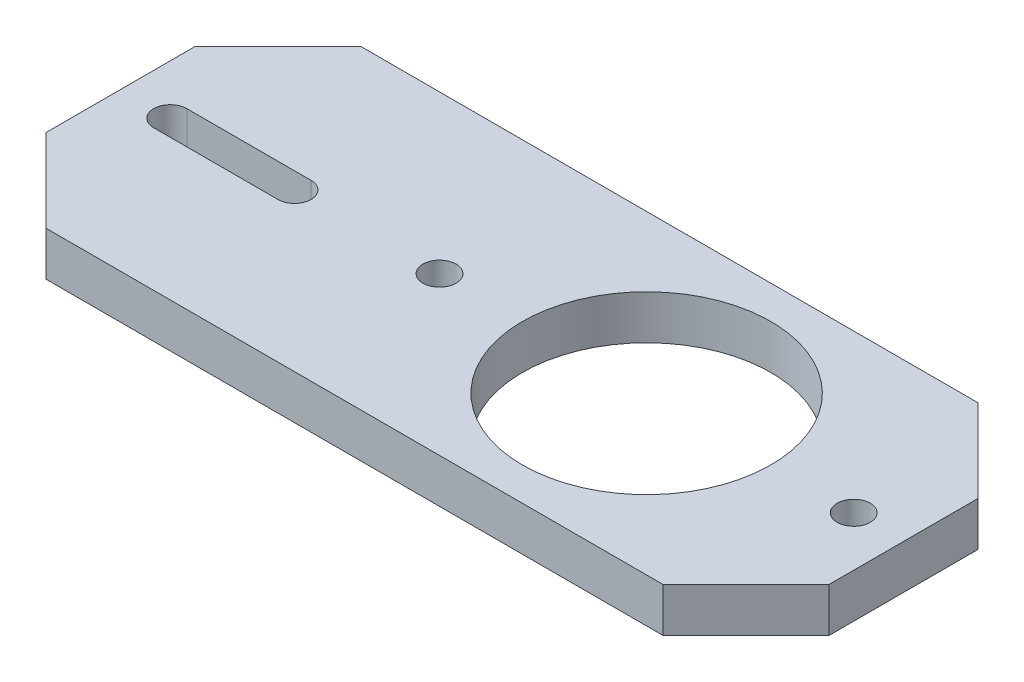
SolidWorks part; units mm, degrees
material "Pine"
ref_plane "Front Plane" through (0, 0, 0) normal (0, 0, 1) x (1, 0, 0)
ref_plane "Top Plane" through (0, 0, 0) normal (0, 1, 0) x (1, 0, 0)
ref_plane "Right Plane" through (0, 0, 0) normal (1, 0, 0) x (0, 0, -1)
sketch "Sketch1" plane through (0, 0, 0) normal (0, 1, 0) x (1, 0, 0)
  line L0 (-57.5, 2) -> (-42.5, 2)
  line L1 (-57.5, -2) -> (-42.5, -2)
  line L2 (-84.5376, 0) -> (67.9764, 0) construction
  line L3 (-50, 2) -> (-50, -2) construction
  line L4 (-63.5, 9) -> (-53.5, 19)
  line L5 (-53.5, 19) -> (21, 19)
  line L6 (-63.5, 9) -> (-63.5, -9)
  line L7 (-53.5, -19) -> (21, -19)
  line L8 (31, 9) -> (31, -9)
  line L9 (-63.5, -9) -> (-53.5, -19)
  line L10 (21, -19) -> (31, -9)
  line L11 (21, 19) -> (31, 9)
  circle A0 centre (-25, 0) radius 2
  circle A1 centre (25, 0) radius 2
  arc A2 (-42.5, -2) -> (-42.5, 2) centre (-42.5, 0) ccw
  arc A4 (-57.5, 2) -> (-57.5, -2) centre (-57.5, 0) ccw
  circle A5 centre (0, 0) radius 15
  point P19 (-63.5, 19)
  point P20 (31, -19)
  point P21 (-63.5, -19)
  point P22 (31, 19)
  dimension "D1" = 4
  dimension "D2" = 4
  dimension "D4" = 4
  dimension "D5" = 75
  dimension "D8" = 4
  dimension "D10" = 30
  dimension "D12" = 6
  dimension "D3" = 50
  dimension "D6" = 15
  dimension "D7" = 6
  dimension "D11" = 25
  dimension "D14" = 19
  dimension "D15" = 19
extrude "Boss-Extrude1" add sketch "Sketch1" against normal blind 5.333
equation "\"rod_diameter\"= 8"
equation "\"rod_hole_thickness\"= 4"
equation "\"rod_radius\"= \"rod_diameter\" / 2"
equation "\"platter_diameter\"= 320"
equation "\"platter_radius\"= \"platter_diameter\" / 2"
equation "\"extruder_mount_hole_spacing\"= 75"
equation "\"arm_rod_spacing\"= 40"
equation "\"motor_level_rod_spacing\"= 15"
equation "\"linear_bearing_diameter\"= 15"
equation "\"z_rod_spacing\"= 75"
equation "\"platter_rod_spacing\"= 50"
equation "\"rod_nut_thickness\"= 6.5"
equation "\"rod_nut_inscribed_diameter\"= 13"
equation "\"z_height\"= 400"
equation "\"gear_pitch\"=2"
equation "\"r_gear_teeth\"= 450"
equation "\"theta_gear_teeth\"= 385"
equation "\"D12@Sketch1\"=2 + \"rod_hole_thickness\""
equation "\"D14@Sketch1\"=15 +\"rod_hole_thickness\""
equation "\"D15@Sketch1\" = 15 + \"rod_hole_thickness\""
equation "\"D7@Sketch1\"=\"rod_hole_thickness\"+2"
equation "\"D5@Sketch1\"=\"extruder_mount_hole_spacing\""
equation "\"top_frame_spacing\"= 100"
equation "\"z_drive_rod_offset\"= 12"
equation "\"sheet_thickness\"=5.333"
equation "\"sheet_tab_hole_thickness\"= \"sheet_thickness\""
equation "\"sheet_tab_width\"= \"sheet_thickness\"*2"
equation "\"sheet_double_tab_width\"= 35"
equation "\"sheet_bolt_diameter\"= 3"
equation "\"sheet_bolt_length\"= 16"
equation "\"sheet_nut_diameter\"= 5.5"
equation "\"sheet_nut_thickness\"= 2.5"
equation "\"sheet_nut_depth\"= 10"
equation "\"bearing_outside_diameter\"= 22"
equation "\"bearing_thickness\"= 7"
equation "\"corner_part_thickness\"= \"sheet_thickness\" + \"bearing_thickness\""
equation "\"setscrew_nut_diameter\"= 6"
equation "\"setscrew_nut_thickness\"= 3"
equation "\"setscrew_bolt_diameter\"= 3"
equation "\"motor_shaft_diameter\"= 5.7"
equation "\"D1@Boss-Extrude1\"= \"sheet_thickness\""
